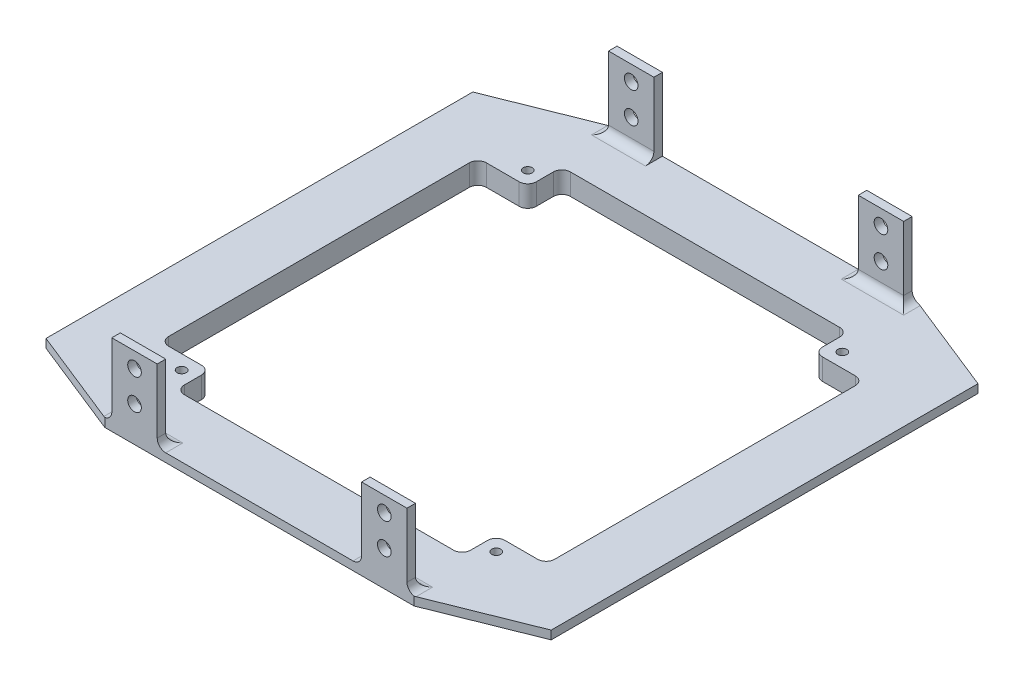
SolidWorks part; units mm, degrees
ref_plane "Front Plane" through (0, 0, 0) normal (0, 0, 1) x (1, 0, 0)
ref_plane "Top Plane" through (0, 0, 0) normal (0, 1, 0) x (1, 0, 0)
ref_plane "Right Plane" through (0, 0, 0) normal (1, 0, 0) x (0, 0, -1)
sketch "Sketch1" plane through (0, 0, 0) normal (0, 1, 0) x (1, 0, 0)
  line L5 (-35.5, 0) -> (0, 0) construction
  line L6 (-25.5, -35.5) -> (25.5, -35.5)
  line L10 (-35.5, -31.5) -> (-35.5, 31.5)
  line L11 (-25.5, 35.5) -> (25.5, 35.5)
  line L12 (35.5, -31.5) -> (35.5, 31.5)
  line L13 (0, 0) -> (0, 35.5) construction
  line L14 (25.5, -35.5) -> (35.5, -31.5)
  line L15 (25.5, 35.5) -> (35.5, 31.5)
  line L16 (-25.5, -35.5) -> (-35.5, -31.5)
  line L17 (-25.5, 35.5) -> (-35.5, 31.5)
  point P0 (0, 0)
  point P4 (35.5, -35.5)
  dimension "D3" = 4
  dimension "D2" = 10
  dimension "D4" = 71
extrude "Boss-Extrude1" add sketch "Sketch1" along normal mid plane 4.5
sketch "Sketch2" plane through (0, 2.25, 0) normal (0, 1, 0) x (1, 0, 0)
  line L16 (27.2332, -44.5) -> (44.5, -37.5933)
  line L17 (44.5, -37.5933) -> (44.5, 37.5933)
  line L18 (44.5, 37.5933) -> (27.2332, 44.5)
  line L19 (27.2332, 44.5) -> (-27.2332, 44.5)
  line L20 (-27.2332, 44.5) -> (-44.5, 37.5933)
  line L21 (-44.5, 37.5933) -> (-44.5, -37.5933)
  line L22 (-44.5, -37.5933) -> (-27.2332, -44.5)
  line L23 (-27.2332, -44.5) -> (27.2332, -44.5)
  line L24 (27.2332, -44.5) -> (44.5, -37.5933)
  line L25 (44.5, -37.5933) -> (44.5, 37.5933)
  line L26 (44.5, 37.5933) -> (27.2332, 44.5)
  line L27 (27.2332, 44.5) -> (-27.2332, 44.5)
  line L28 (-27.2332, 44.5) -> (-44.5, 37.5933)
  line L29 (-44.5, 37.5933) -> (-44.5, -37.5933)
  line L30 (-44.5, -37.5933) -> (-27.2332, -44.5)
  line L31 (-27.2332, -44.5) -> (27.2332, -44.5)
  dimension "D1" = 9
extrude "Boss-Extrude2" add sketch "Sketch2" along normal blind 1.5
mirror "Mirror1" about plane through (0, 0, 0) normal (0, 1, 0) of "Boss-Extrude2"
sketch "Sketch3" plane through (0, 0, 0) normal (0, 1, 0) x (1, 0, 0)
  line L16 (-25.2111, -34) -> (25.2111, -34)
  line L17 (25.2111, -34) -> (34, -30.4845)
  line L18 (34, -30.4845) -> (34, 30.4845)
  line L19 (34, 30.4845) -> (25.2111, 34)
  line L20 (25.2111, 34) -> (-25.2111, 34)
  line L21 (-25.2111, 34) -> (-34, 30.4845)
  line L22 (-34, 30.4845) -> (-34, -30.4845)
  line L23 (-34, -30.4845) -> (-25.2111, -34)
  line L24 (-25.2111, -34) -> (25.2111, -34)
  line L25 (25.2111, -34) -> (34, -30.4845)
  line L26 (34, -30.4845) -> (34, 30.4845)
  line L27 (34, 30.4845) -> (25.2111, 34)
  line L28 (25.2111, 34) -> (-25.2111, 34)
  line L29 (-25.2111, 34) -> (-34, 30.4845)
  line L30 (-34, 30.4845) -> (-34, -30.4845)
  line L31 (-34, -30.4845) -> (-25.2111, -34)
  dimension "D1" = 10.5
extrude "Cut-Extrude1" cut sketch "Sketch3" against normal through all both and the other way through all
sketch "Sketch5" plane through (0, 0, 0) normal (0, 0, 1) x (1, 0, 0)
  line L0 (0, 0) -> (0, 28.4264) construction
  line L1 (-27.2332, 3.75) -> (27.2332, 3.75) construction
  line L2 (-26, 3.75) -> (-18, 3.75)
  line L3 (-26, 3.75) -> (-26, 16.55)
  line L4 (-26, 16.55) -> (-18, 16.55)
  line L5 (-18, 3.75) -> (-18, 16.55)
  line L6 (-22, 16.55) -> (-22, 9.7096) construction
  line L7 (18, 3.75) -> (18, 16.55)
  line L8 (26, 16.55) -> (18, 16.55)
  line L9 (26, 3.75) -> (26, 16.55)
  line L10 (26, 3.75) -> (18, 3.75)
  dimension "D1" = 22
  dimension "D3" = 12.8
  dimension "D2" = 8
extrude "Boss-Extrude3" add sketch "Sketch5" against normal blind 1.5 from surface starting at face at (0, 3, 44.5)
extrude "Boss-Extrude4" add sketch "Sketch5<2>" along normal blind 1.5 from surface starting at face at (0, 3, -44.5)
sketch "Sketch5<2>" plane through (0, 0, 0) normal (0, 0, 1) x (1, 0, 0) same geometry as "Sketch5"
sketch "Sketch6" plane through (0, 0, 0) normal (0, 0, 1) x (1, 0, 0)
  line L0 (-22, 16.55) -> (-22, 13.85) construction
  line L1 (-18, 16.55) -> (-26, 16.55) construction
  line L2 (0, 0) -> (0, 25.5714) construction
  line L3 (-22, 13.85) -> (-22, 8.45) construction
  circle A0 centre (-22, 13.85) radius 1.2
  circle A1 centre (22, 13.85) radius 1.2
  circle A2 centre (-22, 8.45) radius 1.2
  circle A3 centre (22, 8.45) radius 1.2
  dimension "D1" = 2.4
  dimension "D2" = 2.7
  dimension "D3" = 5.4
extrude "Cut-Extrude3" cut sketch "Sketch6" against normal through all both and the other way through all
fillet "Fillet1" radius 1.5 35 edges at (35.5, 0, 31.5) (25.5, 0, 35.5) (0, 2.25, -35.5) (0, -2.25, -35.5) (35.5, 2.25, 0) (35.5, -2.25, 0) (-35.5, 2.25, 0) (-35.5, -2.25, 0) (0, 2.25, 35.5) (0, -2.25, 35.5) (-25.5, 0, -35.5) (-30.5, 2.25, -33.5) (-35.5, 0, -31.5) (-30.5, -2.25, -33.5) (35.5, 0, -31.5) (30.5, 2.25, -33.5) (25.5, 0, -35.5) (30.5, -2.25, -33.5) (30.5, 2.25, 33.5) (30.5, -2.25, 33.5) (-35.5, 0, 31.5) (-30.5, 2.25, 33.5) (-25.5, 0, 35.5) (-30.5, -2.25, 33.5) (-22, 3.75, -43) (22, 3.75, -43) (-22, 3.75, 43) (22, 3.75, 43) (26, 3.75, 43.75) (-18, 3.75, 43.75) (18, 3.75, 43.75) (-26, 3.75, 43.75) (18, 3.75, -43.75) (26, 3.75, -43.75) (-26, 3.75, -43.75)
sketch "Sketch7" plane through (0, 0, 0) normal (0, 1, 0) x (1, 0, 0)
  line L0 (44.5, -37.5933) -> (44.5, 37.5933) construction
  line L1 (-44.5, 44.5) -> (44.5, 44.5)
  line L2 (-44.5, 44.5) -> (-44.5, -44.5)
  line L3 (-44.5, -44.5) -> (44.5, -44.5)
  line L4 (44.5, 44.5) -> (44.5, -44.5)
  line L5 (-44.5, 44.5) -> (44.5, -44.5) construction
  line L6 (-44.5, -44.5) -> (44.5, 44.5) construction
  line L7 (-16.5, -44.5) -> (16.5, -44.5) construction
  point P1 (0, 0)
extrude "Cut-Extrude4" cut sketch "Sketch7" against normal through all
sketch "Sketch8" plane through (0, 0, 0) normal (0, 1, 0) x (1, 0, 0)
  line L0 (-25.2111, -34) -> (-34, -30.4845)
  line L1 (-34, -30.4845) -> (-34, -27.9845)
  line L2 (-34, 30.4845) -> (-34, -30.4845) construction
  line L3 (-34, -27.9845) -> (-25.2111, -27.9845)
  line L4 (-25.2111, -27.9845) -> (-25.2111, -34)
  line L5 (0, 44.5) -> (0, -44.5) construction
  line L6 (-16.5, -44.5) -> (16.5, -44.5) construction
  line L7 (-44.5, 0) -> (44.5, 0) construction
  line L8 (44.5, -37.5933) -> (44.5, 37.5933) construction
  line L9 (-34, -30.4845) -> (-25.2111, -30.4845) construction
  line L10 (34, -30.4845) -> (25.2111, -30.4845) construction
  line L11 (25.2111, -27.9845) -> (25.2111, -34)
  line L12 (34, -27.9845) -> (25.2111, -27.9845)
  line L13 (34, -30.4845) -> (34, -27.9845)
  line L14 (25.2111, -34) -> (34, -30.4845)
  line L15 (34, 30.4845) -> (25.2111, 30.4845) construction
  line L16 (-34, 30.4845) -> (-25.2111, 30.4845) construction
  line L17 (25.2111, 34) -> (34, 30.4845)
  line L18 (34, 30.4845) -> (34, 27.9845)
  line L19 (34, 27.9845) -> (25.2111, 27.9845)
  line L20 (25.2111, 27.9845) -> (25.2111, 34)
  line L21 (-25.2111, 27.9845) -> (-25.2111, 34)
  line L22 (-34, 27.9845) -> (-25.2111, 27.9845)
  line L23 (-34, 30.4845) -> (-34, 27.9845)
  line L24 (-25.2111, 34) -> (-34, 30.4845)
  point P4 (-27.7111, -30.4845)
  point P14 (0, 0)
  point P20 (0, 0)
  point P22 (0, 0)
  point P25 (27.7111, -30.4845)
  point P26 (0, 0)
  point P34 (-27.7111, 30.4845)
  point P35 (27.7111, 30.4845)
  dimension "D2" = 2.5
  dimension "D1" = 2.5
extrude "Boss-Extrude5" add sketch "Sketch8" along normal up to surface (3.75 mm away) up to face at (0, 3.75, 0)
fillet "Fillet2" radius 1.5 12 edges at (-34, 1.875, 27.9845) (-25.2111, 1.875, 34) (25.2111, 1.875, 34) (34, 1.875, 27.9845) (25.2111, 1.875, -34) (34, 1.875, -27.9845) (-34, 1.875, -27.9845) (-25.2111, 1.875, -34) (25.2111, 1.875, -27.9845) (-25.2111, 1.875, -27.9845) (-25.2111, 1.875, 27.9845) (25.2111, 1.875, 27.9845)
hole_wizard "M2x0.4 Tapped Hole1" positions "Sketch11" profile "Sketch12" tap size "M2x0.4" standard "ANSI Metric" end condition through all
sketch "Sketch11" plane through (0, 3.75, 0) normal (0, 1, 0) x (1, 0, 0)
  point P0 (-27.7111, 30.4845)
  point P3 (27.7111, 30.4845)
  point P6 (27.7111, -30.4845)
  point P9 (-27.7111, -30.4845)
sketch "Sketch12" plane through (-27.7111, 3.75, -30.4845) normal (1, 0, 0) x (0, 0, 1)
  line L0 (0, 0) -> (0, 3.75)
  line L1 (0, 3.75) -> (0.8, 3.75)
  line L2 (0.8, 3.75) -> (0.8, 0)
  line L5 (0.8, 0) -> (0, 0)
  line L11 (0, -6.35) -> (0, 107.95) construction
  dimension "Thru Tap Drill Dia." = 1.6
  dimension "Thru Tap Drill Depth" = 3.75
cosmetic thread "Hole Thread1" parameters "D2"=2
cosmetic thread "Hole Thread2" parameters "D2"=2
cosmetic thread "Hole Thread3" parameters "D2"=2
cosmetic thread "Hole Thread4" parameters "D2"=2
